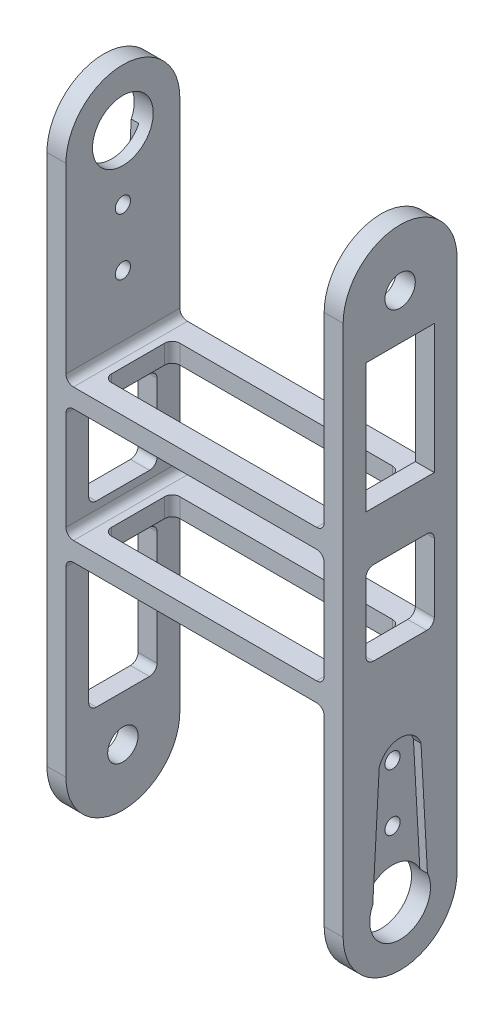
SolidWorks part; units mm, degrees
ref_plane "前视基准面" through (0, 0, 0) normal (0, 0, 1) x (1, 0, 0)
ref_plane "上视基准面" through (0, 0, 0) normal (0, 1, 0) x (1, 0, 0)
ref_plane "右视基准面" through (0, 0, 0) normal (1, 0, 0) x (0, 0, -1)
sketch "草图1" plane through (0, 0, 0) normal (0, 1, 0) x (1, 0, 0)
  line L0 (-16.5, 0) -> (16.5, 0) construction
  point P4 (0, 0)
  dimension "D1" = 33
ref_plane "基准面1" through (17, 0, 0) normal (1, 0, 0) x (0, 0, -1)
ref_plane "基准面2" through (-17, 0, 0) normal (-1, 0, 0) x (0, 0, 1)
sketch "草图4" plane through (-17, 0, 0) normal (-1, 0, 0) x (0, 0, 1)
  line L0 (0, 0) -> (0, -50000) construction
  line L1 (7.5, 70) -> (-7.5, 70) construction
  line L2 (-7.5, 70) -> (-7.5, 0)
  line L3 (-7.5, 0) -> (7.5, 0) construction
  line L4 (7.5, 0) -> (7.5, 70)
  circle A0 centre (0, 0) radius 7.5 construction
  circle A1 centre (0, 70) radius 7.5 construction
  arc A2 (7.5, 70) -> (-7.5, 70) centre (0, 70) ccw
  arc A3 (7.5, 0) -> (-7.5, 0) centre (0, 0) cw
  point P3 (0, 70)
  dimension "D1" = 15
  dimension "D2" = 70
  dimension "D3" = 15
sketch "草图5" plane through (17, 0, 0) normal (1, 0, 0) x (0, 0, -1)
  line L0 (7.5, 0) -> (-7.5, 0) construction
  line L1 (0, 0) -> (0, 29.9674) construction
  line L2 (-7.5, 70) -> (7.5, 70) construction
  line L3 (-7.5, 0) -> (-7.5, 70)
  line L4 (7.5, 70) -> (7.5, 0)
  circle A0 centre (0, 0) radius 7.5 construction
  circle A1 centre (0, 70) radius 7.5 construction
  arc A2 (-7.5, 0) -> (7.5, 0) centre (0, 0) ccw
  arc A3 (-7.5, 70) -> (7.5, 70) centre (0, 70) cw
  point P6 (0, 0)
  point P7 (0, 70)
  point P14 (0, 70)
  dimension "D1" = 15
  dimension "D2" = 70
  dimension "D3" = 15
extrude "凸台-拉伸1" add sketch "草图4" along normal blind 2.5
sketch "草图6" plane through (-19.5, 0, 0) normal (-1, 0, 0) x (0, 0, 1)
  circle A0 centre (0, 0) radius 2
  dimension "D1" = 4
extrude "切除-拉伸1" cut sketch "草图6" against normal blind 3
extrude "凸台-拉伸2" add sketch "草图5" along normal blind 2.5 separate body
sketch "草图7" plane through (19.5, 0, 0) normal (1, 0, 0) x (0, 0, -1)
  line L0 (0, 0) -> (0, 2.3395) construction
  line L1 (3.6, 1.7436) -> (-3.6, 1.7436) construction
  line L2 (-2.75, 17) -> (2.75, 17) construction
  line L3 (-3.6, 1.7436) -> (-2.75, 17)
  line L4 (3.6, 1.7436) -> (2.75, 17)
  circle A0 centre (0, 0) radius 4 construction
  arc A1 (-3.6, 1.7436) -> (3.6, 1.7436) centre (0, 0) ccw
  arc A2 (-2.75, 17) -> (2.75, 17) centre (0, 16.1094) cw
  point P4 (0, 19)
  point P6 (0, 17)
  point P10 (0, 1.7436)
  point P13 (0, 17)
  point P15 (0, -4)
  point P16 (0, 0)
  dimension "D1" = 8
  dimension "D2" = 23
  dimension "D3" = 2
  dimension "D4" = 7.2
  dimension "D5" = 5.5
extrude "切除-拉伸2" cut sketch "草图7" against normal blind 1
sketch "草图8" plane through (18.5, 0, 0) normal (1, 0, 0) x (0, 0, -1)
  line L0 (0, 0) -> (0, 50000) construction
  circle A0 centre (0, 0) radius 4
  circle A1 centre (0, 15.95) radius 1
  circle A2 centre (0, 8.45) radius 1
  point P6 (0, 15.95)
  point P7 (0, 8.45)
  dimension "D1" = 8
  dimension "D3" = 2
  dimension "D5" = 2
  dimension "D2" = 15.95
  dimension "D4" = 7.5
extrude "切除-拉伸3" cut sketch "草图8" against normal up to next
sketch "草图9" plane through (19.5, 0, 0) normal (1, 0, 0) x (0, 0, -1)
  circle A0 centre (0, 70) radius 2
  arc A1 (7.5, 70) -> (-7.5, 70) centre (0, 70) ccw construction
  dimension "D1" = 4
extrude "切除-拉伸4" cut sketch "草图9" against normal up to next
sketch "草图10" plane through (-19.5, 0, 0) normal (-1, 0, 0) x (0, 0, 1)
  line L0 (0, 69.716) -> (0, -49930.284) construction
  line L1 (3.6, 68.2564) -> (-3.6, 68.2564) construction
  line L2 (-2.75, 53.385) -> (2.75, 53.385) construction
  line L3 (3.6, 68.2564) -> (2.75, 53.385)
  line L4 (-3.6, 68.2564) -> (-2.75, 53.385)
  circle A0 centre (0, 70) radius 4 construction
  arc A1 (7.5, 70) -> (-7.5, 70) centre (0, 70) ccw construction
  arc A2 (2.75, 53.385) -> (-2.75, 53.385) centre (0, 53.7779) cw
  arc A3 (3.6, 68.2564) -> (-3.6, 68.2564) centre (0, 70) ccw
  point P2 (0, 74)
  point P6 (0, 51)
  point P11 (0, 53.385)
  point P15 (0, 53.385)
  dimension "D1" = 8
  dimension "D2" = 23
  dimension "D3" = 5.5
  dimension "D4" = 7.2
extrude "切除-拉伸5" cut sketch "草图10" against normal blind 1
sketch "草图11" plane through (-18.5, 0, 0) normal (-1, 0, 0) x (0, 0, 1)
  line L0 (0, 70) -> (0, 62.0556) construction
  circle A0 centre (0, 70) radius 4
  arc A1 (3.6, 68.2564) -> (-3.6, 68.2564) centre (0, 70) ccw construction
  circle A2 centre (0, 54.05) radius 1
  circle A3 centre (0, 61.55) radius 1
  point P6 (0, 61.55)
  point P9 (0, 54.05)
  dimension "D1" = 8
  dimension "D4" = 2
  dimension "D5" = 2
  dimension "D2" = 15.95
  dimension "D3" = 7.5
extrude "切除-拉伸6" cut sketch "草图11" against normal up to next
ref_axis "基准轴1" through (17, 70, 0) along (1, 0, 0)
ref_axis "基准轴2" through (-17, 0, 0) along (-1, 0, 0)
ref_plane "基准面6" through (0, 70, 0) normal (0, 1, 0) x (1, 0, 0)
ref_plane "基准面5" through (0, 35, 0) normal (0, 1, 0) x (1, 0, 0)
sketch "草图12" plane through (0, 0, 0) normal (0, 0, 1) x (1, 0, 0)
  line L0 (17, -8.25) -> (17, 8.25) construction
  line L1 (17, 45) -> (-17, 45) construction
  line L2 (17, 45) -> (17, 25) construction
  line L3 (17, 25) -> (-17, 25) construction
  line L4 (-17, 45) -> (-17, 25) construction
  line L5 (17, 45) -> (-17, 25) construction
  line L6 (17, 25) -> (-17, 45) construction
  line L7 (-17, 8.25) -> (-17, -8.25) construction
  line L11 (55, 35) -> (-55, 35) construction
  line L12 (17, 45) -> (-17, 45)
  line L13 (17, 45) -> (17, 42.5)
  line L14 (17, 42.5) -> (-17, 42.5)
  line L15 (-17, 45) -> (-17, 42.5)
  line L16 (17, 45) -> (-17, 42.5) construction
  line L17 (17, 42.5) -> (-17, 45) construction
  line L18 (17, 25) -> (-17, 25)
  line L19 (17, 25) -> (17, 27.5)
  line L20 (17, 27.5) -> (-17, 27.5)
  line L21 (-17, 25) -> (-17, 27.5)
  line L22 (17, 25) -> (-17, 27.5) construction
  line L23 (17, 27.5) -> (-17, 25) construction
  point P4 (0, 35)
  point P13 (0, 43.75)
  point P14 (0, 26.25)
  point P15 (0, 0)
  point P16 (0, 0)
  dimension "D2" = 20
  dimension "D3" = 2.5
  dimension "D4" = 2.5
extrude "凸台-拉伸3" add sketch "草图12" along normal up to surface and the other way up to surface up to face at (-18.25, 35, 7.5) other way up to face at (-18.25, 35, -7.5)
sketch "草图13" plane through (-19.5, 0, 0) normal (-1, 0, 0) x (0, 0, 1)
  line L0 (7.5, 0) -> (7.5, 70) construction
  line L1 (4.5, 23) -> (-4.5, 23)
  line L2 (4.5, 23) -> (4.5, 6)
  line L3 (4.5, 6) -> (-4.5, 6)
  line L4 (-4.5, 23) -> (-4.5, 6)
  line L5 (4.5, 23) -> (-4.5, 6) construction
  line L6 (4.5, 6) -> (-4.5, 23) construction
  line L7 (55, 35) -> (-55, 35) construction
  line L8 (4.5, 40.5) -> (-4.5, 40.5)
  line L9 (4.5, 40.5) -> (4.5, 29.5)
  line L10 (4.5, 29.5) -> (-4.5, 29.5)
  line L11 (-4.5, 40.5) -> (-4.5, 29.5)
  line L12 (4.5, 40.5) -> (-4.5, 29.5) construction
  line L13 (4.5, 29.5) -> (-4.5, 40.5) construction
  line L18 (7.5, 25) -> (-7.5, 25) construction
  line L19 (7.5, 27.5) -> (-7.5, 27.5) construction
  point P4 (0, 14.5)
  point P5 (0, 0)
  point P13 (0, 35)
  point P14 (0, 0)
  point P17 (0, 0)
  dimension "D1" = 7.5
  dimension "D2" = 9
  dimension "D3" = 6
  dimension "D4" = 2
  dimension "D5" = 9
  dimension "D6" = 7.5
  dimension "D7" = 2
extrude "切除-拉伸7" cut sketch "草图13" against normal up to surface (19.5 mm away) up to plane "右视基准面"
sketch "草图14" plane through (19.5, 0, 0) normal (1, 0, 0) x (0, 0, -1)
  line L0 (-7.5, 70) -> (-7.5, 0) construction
  line L1 (-4.5, 47) -> (4.5, 47)
  line L2 (-4.5, 47) -> (-4.5, 64)
  line L3 (-4.5, 64) -> (4.5, 64)
  line L4 (4.5, 47) -> (4.5, 64)
  line L5 (-4.5, 47) -> (4.5, 64) construction
  line L6 (-4.5, 64) -> (4.5, 47) construction
  line L7 (-4.5, 29.5) -> (4.5, 29.5)
  line L8 (-4.5, 29.5) -> (-4.5, 40.5)
  line L9 (-4.5, 40.5) -> (4.5, 40.5)
  line L10 (4.5, 29.5) -> (4.5, 40.5)
  line L11 (-4.5, 29.5) -> (4.5, 40.5) construction
  line L12 (-4.5, 40.5) -> (4.5, 29.5) construction
  line L13 (55, 35) -> (-55, 35) construction
  line L14 (-7.5, 45) -> (7.5, 45) construction
  line L15 (-7.5, 42.5) -> (7.5, 42.5) construction
  point P4 (0, 55.5)
  point P9 (0, 35)
  point P13 (0, 0)
  dimension "D1" = 6
  dimension "D2" = 2
  dimension "D3" = 9
  dimension "D4" = 7.5
  dimension "D5" = 7.5
  dimension "D6" = 9
  dimension "D7" = 2
extrude "切除-拉伸8" cut sketch "草图14" against normal up to next and the other way through all
sketch "草图15" plane through (0, 35, 0) normal (0, 1, 0) x (1, 0, 0)
  line L1 (-15, -4.5) -> (15, -4.5)
  line L2 (-15, -4.5) -> (-15, 4.5)
  line L3 (-15, 4.5) -> (15, 4.5)
  line L4 (15, -4.5) -> (15, 4.5)
  line L5 (-15, -4.5) -> (15, 4.5) construction
  line L6 (-15, 4.5) -> (15, -4.5) construction
  line L8 (17, 7.5) -> (-17, 7.5) construction
  point P4 (0, 0)
  dimension "D1" = 3
  dimension "D2" = 30
extrude "切除-拉伸9" cut sketch "草图15" against normal through all both and the other way through all
fillet "圆角1" radius 1 28 edges at (-17, 25, 0) (17, 25, 0) (17, 27.5, 0) (-17, 27.5, 0) (18.25, 29.5, -4.5) (18.25, 40.5, -4.5) (18.25, 40.5, 4.5) (18.25, 29.5, 4.5) (-18.25, 6, -4.5) (-18.25, 6, 4.5) (-18.25, 23, -4.5) (-18.25, 23, 4.5) (-15, 26.25, 4.5) (-15, 26.25, -4.5) (15, 26.25, -4.5) (15, 26.25, 4.5) (-18.25, 40.5, 4.5) (-18.25, 40.5, -4.5) (-18.25, 29.5, -4.5) (-18.25, 29.5, 4.5) (-17, 42.5, 0) (17, 42.5, 0) (15, 43.75, -4.5) (-15, 43.75, -4.5) (-15, 43.75, 4.5) (15, 43.75, 4.5) (17, 45, 0) (-17, 45, 0)
